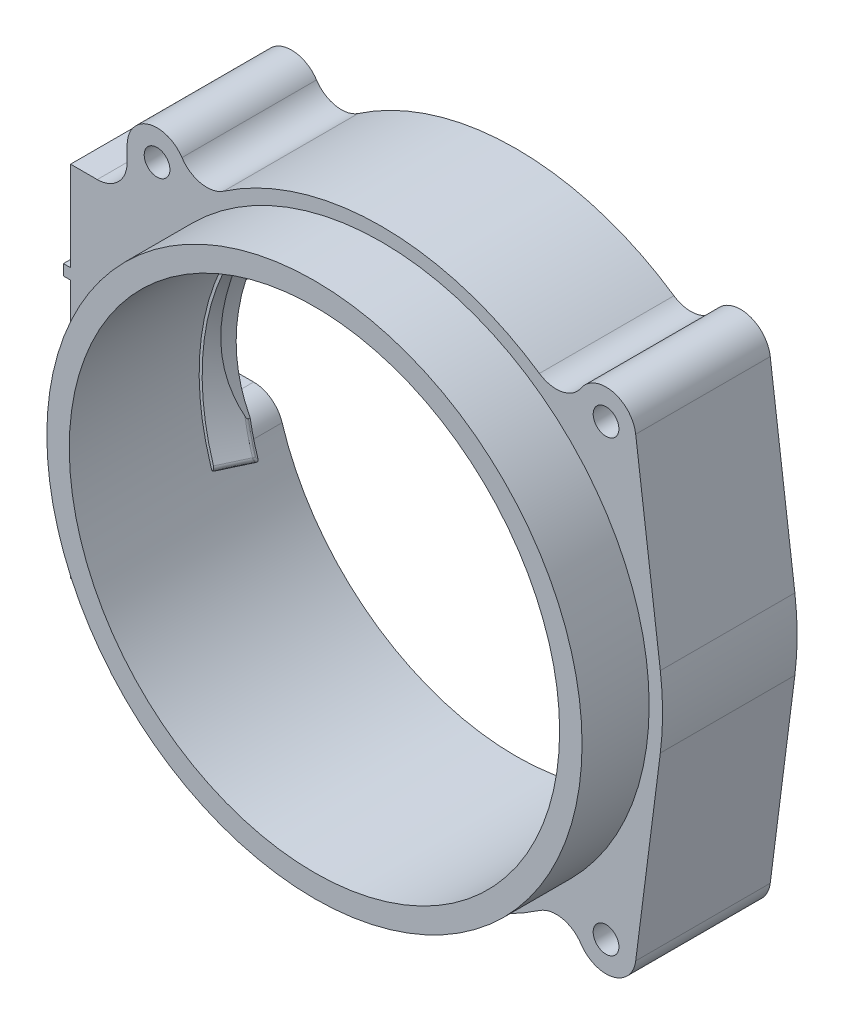
SolidWorks part; units mm, degrees
ref_plane "前视基准面" through (0, 0, 0) normal (0, 0, 1) x (1, 0, 0)
ref_plane "上视基准面" through (0, 0, 0) normal (0, 1, 0) x (1, 0, 0)
ref_plane "右视基准面" through (0, 0, 0) normal (1, 0, 0) x (0, 0, -1)
sketch "草图1" plane through (0, 0, 0) normal (0, 0, 1) x (1, 0, 0)
  line L0 (0, 0) -> (50000, 0) construction
  line L1 (-52, 8.75) -> (-52, -8.75) construction
  line L2 (-52, 8.75) -> (-52, 30)
  line L3 (-52, -8.75) -> (-52, -30)
  line L4 (-52, 8.75) -> (-43.8969, 8.75)
  line L5 (-52, -8.75) -> (-43.8969, -8.75)
  line L6 (-42.54, 37.5) -> (-42.54, 35)
  line L7 (-47.54, 30) -> (-52, 30)
  line L8 (-47.54, -30) -> (-52, -30)
  line L9 (-42.54, -37.5) -> (-42.54, -35)
  line L10 (0, 0) -> (0, -50000) construction
  line L11 (42.4995, 38.1352) -> (46.6192, 5.9711)
  line L12 (42.4995, -38.1352) -> (46.6192, -5.9711)
  arc A0 (-39.1255, -12.2554) -> (-39.1255, 12.2554) centre (0, 0) ccw
  arc A1 (-40.0554, 8.75) -> (-40.0554, -8.75) centre (0, 0) ccw construction
  circle A2 centre (-37.54, 37.5) radius 2.15
  circle A3 centre (-37.54, -37.5) radius 2.15
  arc A4 (-33.3722, 40.2622) -> (-42.54, 37.5) centre (-37.54, 37.5) ccw
  arc A5 (-42.54, -37.5) -> (-33.3722, -40.2622) centre (-37.54, -37.5) ccw
  arc A6 (-26.3963, -38.8874) -> (26.3963, -38.8874) centre (0, 0) ccw
  arc A7 (-33.3722, 40.2622) -> (-26.3963, 38.8874) centre (-29.2045, 43.0244) ccw
  arc A8 (-33.3722, -40.2622) -> (-42.54, -37.5) centre (-37.54, -37.5) cw
  arc A9 (-33.3722, -40.2622) -> (-26.3963, -38.8874) centre (-29.2045, -43.0244) cw
  circle A10 centre (37.54, -37.5) radius 2.15
  circle A11 centre (37.54, 37.5) radius 2.15
  arc A12 (42.4995, 38.1352) -> (33.3722, 40.2622) centre (37.54, 37.5) ccw
  arc A13 (33.3722, -40.2622) -> (42.4995, -38.1352) centre (37.54, -37.5) ccw
  arc A14 (33.3722, 40.2622) -> (26.3963, 38.8874) centre (29.2045, 43.0244) cw
  arc A15 (33.3722, -40.2622) -> (26.3963, -38.8874) centre (29.2045, -43.0244) ccw
  arc A16 (26.3963, 38.8874) -> (-26.3963, 38.8874) centre (0, 0) ccw
  arc A17 (46.6192, -5.9711) -> (46.6192, 5.9711) centre (0, 0) ccw
  arc A18 (-47.54, -30) -> (-42.54, -35) centre (-47.54, -35) cw
  arc A19 (-42.54, 35) -> (-47.54, 30) centre (-47.54, 35) cw
  arc A20 (-43.8969, 8.75) -> (-39.1255, 12.2554) centre (-43.8969, 13.75) ccw
  arc A21 (-43.8969, -8.75) -> (-39.1255, -12.2554) centre (-43.8969, -13.75) cw
  point P8 (-52, 0)
  point P44 (-42.54, -30)
  point P47 (-42.54, 30)
  dimension "D1" = 82
  dimension "D5" = 4.3
  dimension "D6" = 75
  dimension "D8" = 10
  dimension "D9" = 94
  dimension "D10" = 5
  dimension "D11" = 10
  dimension "D12" = 5
  dimension "D13" = 5
  dimension "D14" = 5
  dimension "D15" = 5
  dimension "D2" = 17.5
  dimension "D3" = 52
  dimension "D4" = 60
  dimension "D7" = 14.46
extrude "凸台-拉伸1" add sketch "草图1" along normal blind 22.5 contours A21 L5 L3 L8 A18 L9 A5 A9 A6 A15 A13 L12 A17 L11 A12 A14 A16 A7 A4 L6 A19 L7 L2 L4 A20 A0 A10 A3 A2 A11 region at (-50.6348, 19.375, 0)
sketch "草图3" plane through (0, 0, 22.5) normal (0, 0, 1) x (1, 0, 0)
  line L0 (-52, -8.75) -> (-43.8969, -8.75) construction
  line L1 (-52, 8.75) -> (-43.8969, 8.75) construction
  line L2 (-52, -8.75) -> (-43.8969, -8.75)
  line L3 (-52, 8.75) -> (-43.8969, 8.75)
  line L4 (-52, 8.75) -> (-52, -8.75)
  arc A1 (-39.1255, -12.2554) -> (-43.8969, -8.75) centre (-43.8969, -13.75) ccw construction
  arc A2 (-43.8969, 8.75) -> (-39.1255, 12.2554) centre (-43.8969, 13.75) ccw construction
  arc A3 (-39.1255, -12.2554) -> (-43.8969, -8.75) centre (-43.8969, -13.75) ccw
  arc A4 (-43.8969, 8.75) -> (-39.1255, 12.2554) centre (-43.8969, 13.75) ccw
  arc A5 (-39.1255, 12.2554) -> (-39.1255, -12.2554) centre (0, 0) ccw
  arc A6 (-39.1255, -12.2554) -> (-39.1255, 12.2554) centre (0, 0) ccw construction
extrude "凸台-拉伸2" add sketch "草图3" against normal blind 14.5
sketch "草图4" plane through (-52, 0, 0) normal (-1, 0, 0) x (0, 0, 1)
  line L0 (0, 0) -> (-50000, 0) construction
  line L1 (22.5, 30) -> (22.5, -30) construction
  line L2 (22.5, 15) -> (8, 15)
  line L3 (22.5, 15) -> (22.5, 13.2)
  line L4 (22.5, 13.2) -> (8, 13.2)
  line L5 (8, 15) -> (8, 13.2)
  line L7 (22.5, -15) -> (8, -15)
  line L8 (22.5, -15) -> (22.5, -13.2)
  line L9 (22.5, -13.2) -> (8, -13.2)
  line L10 (8, -15) -> (8, -13.2)
  dimension "D1" = 26.4
  dimension "D2" = 14.5
  dimension "D3" = 1.8
extrude "凸台-拉伸3" add sketch "草图4" along normal blind 1.2
sketch "草图5" plane through (0, 0, 22.5) normal (0, 0, 1) x (1, 0, 0)
  circle A0 centre (0, 0) radius 44.75
  circle A1 centre (0, 0) radius 41
  dimension "D1" = 89.5
  dimension "D2" = 82
extrude "凸台-拉伸4" add sketch "草图5" along normal blind 11.22
sketch "草图6" plane through (0, 0, 8) normal (0, 0, -1) x (-1, 0, 0)
  line L0 (0, 0) -> (50000, 0) construction
  line L1 (0, 0) -> (0, -50000) construction
  line L2 (0, 0) -> (34.9842, -12.046) construction
  line L3 (34.9842, -12.046) -> (38.7663, -13.3483)
  line L4 (0, 0) -> (27.9243, 24.2742) construction
  line L5 (30.9431, 26.8984) -> (27.9243, 24.2742)
  arc A0 (34.9842, -12.046) -> (27.9243, 24.2742) centre (0, 0) ccw
  arc A1 (39.1255, 12.2554) -> (39.1255, -12.2554) centre (0, 0) ccw construction
  arc A2 (38.7663, -13.3483) -> (30.9431, 26.8984) centre (0, 0) ccw
  dimension "D1" = 37
  dimension "D2" = 19
  dimension "D3" = 41
extrude "凸台-拉伸5" add sketch "草图6" against normal blind 4
chamfer "倒角1" distance 3.5 angle 45 1 edges at (-36.3202, 7.0599, 12)
fillet "圆角1" radius 1 1 edges at (-36.6388, -12.6158, 10.25)
fillet "圆角2" radius 0.5 2 edges at (-35.1439, -11.5717, 8.3208) (-36.2234, 7.541, 8.5)
sketch "草图7" plane through (0, 0, 12) normal (0, 0, 1) x (1, 0, 0)
  line L0 (-38.7663, -13.3483) -> (-35.8361, -12.3394) construction
  line L1 (-30.9431, 26.8984) -> (-27.9243, 24.2742)
  arc A0 (-27.9243, 24.2742) -> (-35.2902, -11.1176) centre (0, 0) ccw construction
  arc A1 (-27.9243, 24.2742) -> (-36.4745, -6.2135) centre (0, 0) ccw
  spline S0 degree 3 poles (-36.4745, -6.2135) (-42.0845, 4.603) (-36.5338, 17.4065) (-30.9431, 26.8984) knots 0 0 0 0 1 1 1 1
  dimension "D1" = 6
extrude "切除-拉伸1" cut sketch "草图7" against normal blind 4
